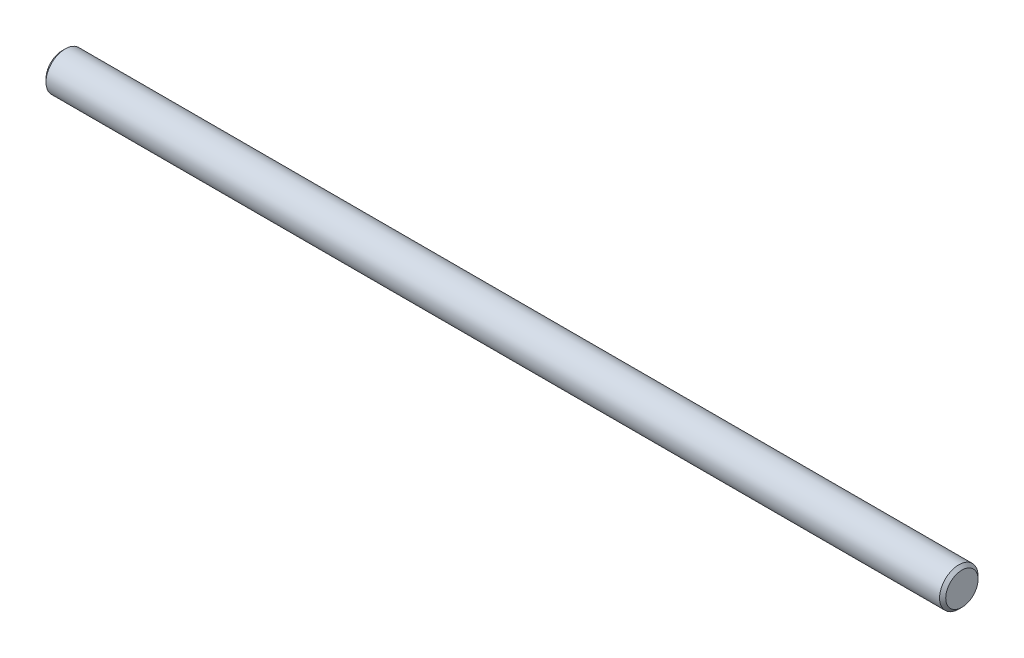
SolidWorks part; units mm, degrees
material "EN 1.3505 Equiv."
ref_plane "Front Plane" through (0, 0, 0) normal (0, 0, 1) x (1, 0, 0)
ref_plane "Top Plane" through (0, 0, 0) normal (0, 1, 0) x (1, 0, 0)
ref_plane "Right Plane" through (0, 0, 0) normal (1, 0, 0) x (0, 0, -1)
sketch "Sketch1" plane through (0, 0, 0) normal (0, 0, 1) x (1, 0, 0)
  line L0 (0, 0) -> (117, 0) construction
  line L3 (0, 0) -> (117, 0)
  line L4 (0, 0) -> (0, 2.5)
  line L5 (0, 2.5) -> (117, 2.5)
  line L6 (117, 0) -> (117, 2.5)
  dimension "D" = 5
  dimension "L" = 117
revolve "Revolve1" add sketch "Sketch1" angle 360 about L0
chamfer "Chamfer1" distance 0.4 angle 45 2 edges at (117, 0, 2.5) (0, 0, 2.5)
ref_plane "Plane1" through (0, 0, 2.5) normal (0, 0, 1) x (1, 0, 0)
ref_plane "Plane2" through (117, 0, 0) normal (1, 0, 0) x (0, 0, -1)
ref_plane "Dim. A" through (2, 0, 0) normal (-1, 0, 0) x (0, 0, 1)
ref_plane "Dim. SC" [suppressed] through (2, 0, 0) normal (-1, 0, 0) x (0, 0, 1)
sketch "Sketch2" [suppressed] plane through (0, 0, 0) normal (0, 1, 0) x (1, 0, 0)
  line L0 (0, 0) -> (76, 0) construction
  line L1 (2, -6) -> (12, -6)
  line L2 (2, -6) -> (2, -5)
  line L3 (2, -5) -> (12, -5)
  line L4 (12, -6) -> (12, -5)
  line L5 (7, -5) -> (7, -6) construction
  line L6 (2, 6) -> (12, 6)
  line L7 (2, 6) -> (2, 5)
  line L8 (2, 5) -> (12, 5)
  line L9 (12, 6) -> (12, 5)
  line L11 (2, 5.5) -> (2, -5.5) construction
  dimension "L1_s" = 10
  dimension "W_1" = 10
  dimension "D" = 5
  dimension "L1_s_L" = 10
extrude "Cut-Extrude1" [suppressed] cut sketch "Sketch2" against normal through all and the other way through all
ref_plane "SC_SEC" [suppressed] through (7, 0, 0) normal (1, 0, 0) x (0, 0, -1)
ref_plane "Dim. WSC" [suppressed] through (2, 0, 0) normal (-1, 0, 0) x (0, 0, 1)
ref_plane "Dim. X" [suppressed] through (74, 0, 0) normal (1, 0, 0) x (0, 0, -1)
sketch "Sketch3" [suppressed] plane through (0, 0, 0) normal (0, 1, 0) x (1, 0, 0)
  line L0 (0, 0) -> (76, 0) construction
  line L1 (2, -6) -> (12, -6)
  line L2 (2, -6) -> (2, -5)
  line L3 (2, -5) -> (12, -5)
  line L4 (12, -6) -> (12, -5)
  line L5 (2, 5.5) -> (2, -5.5) construction
  line L6 (2, 6) -> (12, 6)
  line L7 (2, 6) -> (2, 5)
  line L8 (2, 5) -> (12, 5)
  line L9 (12, 6) -> (12, 5)
  line L10 (7, -5) -> (7, -6) construction
  line L11 (64, 6) -> (74, 6)
  line L12 (64, 6) -> (64, 5)
  line L13 (64, 5) -> (74, 5)
  line L14 (74, 6) -> (74, 5)
  line L15 (64, -6) -> (74, -6)
  line L16 (64, -6) -> (64, -5)
  line L17 (64, -5) -> (74, -5)
  line L18 (74, -6) -> (74, -5)
  line L19 (74, -2.6075) -> (74, 2.6075) construction
  line L20 (69, -5) -> (69, -6) construction
  dimension "L1_s" = 10
  dimension "W_1" = 10
  dimension "D" = 5
  dimension "L1_s_L1" = 10
  dimension "L1_s_R2" = 10
  dimension "L1_s_R1" = 10
  dimension "W_1_R" = 10
extrude "Cut-Extrude2" [suppressed] cut sketch "Sketch3" against normal through all and the other way through all
ref_plane "WSC_SEC1" [suppressed] through (7, 0, 0) normal (1, 0, 0) x (0, 0, -1)
ref_plane "WSC_SEC2" [suppressed] through (69, 0, 0) normal (1, 0, 0) x (0, 0, -1)
sketch "Sketch4" [suppressed] plane through (0, 0, 0) normal (0, 0, 1) x (1, 0, 0)
  line L0 (2, 5.5) -> (2, -5.5) construction
  line L1 (2, 6) -> (7, 6)
  line L2 (2, 6) -> (2, 5)
  line L3 (2, 5) -> (7, 5)
  line L4 (7, 6) -> (7, 5)
  line L5 (0, 0) -> (76, 0) construction
  line L6 (4.5, 6) -> (4.5, 5) construction
  line L7 (0, 6) -> (76, 6) construction
  dimension "FC" = 5
  dimension "H_s_1" = 1
extrude "Cut-Extrude3" [suppressed] cut sketch "Sketch4" against normal through all and the other way through all
ref_plane "FC_SEC" [suppressed] through (4.5, 0, 0) normal (1, 0, 0) x (0, 0, -1)
ref_plane "Dim. E" [suppressed] through (74, 0, 0) normal (1, 0, 0) x (0, 0, -1)
sketch "Sketch5" [suppressed] plane through (0, 0, 0) normal (0, 0, 1) x (1, 0, 0)
  line L0 (4.5, 6) -> (4.5, 5) construction
  line L1 (2, 6) -> (7, 6)
  line L2 (2, 6) -> (2, 5)
  line L3 (2, 5) -> (7, 5)
  line L4 (7, 6) -> (7, 5)
  line L5 (2, 5.5) -> (2, -5.5) construction
  line L6 (74, 6) -> (69, 6)
  line L7 (74, 6) -> (74, 5)
  line L8 (74, 5) -> (69, 5)
  line L9 (69, 6) -> (69, 5)
  line L10 (0, 0) -> (76, 0) construction
  line L11 (71.5, 6) -> (71.5, 5) construction
  line L12 (74, -5.775) -> (74, 5.775) construction
  line L13 (0, 6) -> (76, 6) construction
  dimension "WFC" = 5
  dimension "H_s_1" = 1
  dimension "WFC_R" = 5
  dimension "H_s_1_R" = 1
extrude "Cut-Extrude4" [suppressed] cut sketch "Sketch5" against normal through all and the other way through all
ref_plane "WFC_SEC1" [suppressed] through (4.5, 0, 0) normal (1, 0, 0) x (0, 0, -1)
ref_plane "WFC_SEC2" [suppressed] through (71.5, 0, 0) normal (1, 0, 0) x (0, 0, -1)
sketch "Sketch6" [suppressed] plane through (0, 0, 0) normal (0, 0, 1) x (1, 0, 0)
  line L0 (0, 0) -> (76, 0) construction
  line L1 (2, 6) -> (8, 6)
  line L2 (2, 6) -> (2, 5)
  line L3 (2, 5) -> (8, 5)
  line L4 (8, 6) -> (8, 5)
  line L5 (0, 5.6) -> (0, -5.6) construction
  line L6 (5, 6) -> (5, 5) construction
  dimension "D" = 5
  dimension "H_s_2" = 1
  dimension "B1_s" = 6
  dimension "RC" = 2
extrude "Cut-Extrude5" [suppressed] cut sketch "Sketch6" against normal through all and the other way through all
pattern_circular "CirPattern1" [suppressed] count 2 every 90 reverse direction yes of bodies 106
ref_plane "Plane3" [suppressed] through (0, 0, 0) normal (0, 1, 0) x (1, 0, 0)
sketch "Sketch12" [suppressed] plane through (0, 0, 0) normal (0, 1, 0) x (1, 0, 0)
  line L0 (0, 0) -> (76, 0) construction
  line L1 (2, -6) -> (8, -6)
  line L2 (2, -6) -> (2, -5)
  line L3 (2, -5) -> (8, -5)
  line L4 (8, -6) -> (8, -5)
  dimension "D" = 5
  dimension "H_s_2" = 1
  dimension "B1_s" = 6
  dimension "RC" = 2
ref_plane "RC_SEC" [suppressed] through (5, 0, 0) normal (1, 0, 0) x (0, 0, -1)
sketch "Sketch13" [suppressed] plane through (5, 0, 0) normal (1, 0, 0) x (0, 0, -1)
  line L0 (-6, 0) -> (-5, 0) construction
  line L1 (-6, 0) -> (-5, 0) construction
  line L2 (0, 6) -> (0, 5) construction
  line L3 (0, 6) -> (0, 5) construction
  line L4 (-3.3166, 5) -> (3.3166, 5) construction
  line L5 (-5, 3.3166) -> (-5, -3.3166) construction
  circle A0 centre (0, 0) radius 6 construction
  dimension "ANG" = 90
sketch "Sketch7" [suppressed] plane through (0, 0, 0) normal (0, 0, 1) x (1, 0, 0)
  line L0 (5, 6) -> (5, 5) construction
  line L1 (2, 6) -> (8, 6)
  line L2 (2, 6) -> (2, 5)
  line L3 (2, 5) -> (8, 5)
  line L4 (8, 6) -> (8, 5)
  line L6 (68, 6) -> (74, 6)
  line L7 (68, 6) -> (68, 5)
  line L8 (68, 5) -> (74, 5)
  line L9 (74, 6) -> (74, 5)
  line L11 (0, 0) -> (76, 0) construction
  line L12 (71, 6) -> (71, 5) construction
  dimension "D" = 5
  dimension "H_s_2" = 1
  dimension "B1_s" = 6
  dimension "H_s_2_R" = 1
  dimension "B1_s_R" = 6
  dimension "WRC" = 2
  dimension "Y" = 2
extrude "Cut-Extrude6" [suppressed] cut sketch "Sketch7" against normal through all and the other way through all
pattern_circular "CirPattern2" [suppressed] count 2 every 90 reverse direction yes of bodies 108
ref_plane "Plane4" [suppressed] through (0, 0, 0) normal (0, 1, 0) x (1, 0, 0)
sketch "Sketch14" [suppressed] plane through (0, 0, 0) normal (0, 1, 0) x (1, 0, 0)
  line L0 (0, 0) -> (76, 0) construction
  line L1 (2, -6) -> (8, -6)
  line L2 (2, -6) -> (2, -5)
  line L3 (2, -5) -> (8, -5)
  line L4 (8, -6) -> (8, -5)
  line L5 (68, -6) -> (74, -6)
  line L6 (68, -6) -> (68, -5)
  line L7 (68, -5) -> (74, -5)
  line L8 (74, -6) -> (74, -5)
  dimension "D" = 5
  dimension "H_s_2" = 1
  dimension "B1_s" = 6
  dimension "H_s_2_R" = 1
  dimension "B1_s_R" = 6
  dimension "WRC" = 2
  dimension "Y" = 2
ref_plane "WRC_SEC1" [suppressed] through (5, 0, 0) normal (1, 0, 0) x (0, 0, -1)
sketch "Sketch15" [suppressed] plane through (5, 0, 0) normal (1, 0, 0) x (0, 0, -1)
  line L0 (0, 6) -> (0, 5) construction
  line L1 (-6, 0) -> (-5, 0) construction
  line L2 (0, 6) -> (0, 5) construction
  line L3 (-6, 0) -> (-5, 0) construction
  line L4 (-3.3166, 5) -> (3.3166, 5) construction
  line L5 (-5, 3.3166) -> (-5, -3.3166) construction
  circle A0 centre (0, 0) radius 6 construction
  dimension "ANG_L" = 90
ref_plane "WRC_SEC2" [suppressed] through (71, 0, 0) normal (1, 0, 0) x (0, 0, -1)
sketch "Sketch16" [suppressed] plane through (71, 0, 0) normal (1, 0, 0) x (0, 0, -1)
  line L0 (0, 6) -> (0, 5) construction
  line L1 (-6, 0) -> (-5, 0) construction
  line L2 (0, 6) -> (0, 5) construction
  line L3 (-6, 0) -> (-5, 0) construction
  line L4 (-3.3166, 5) -> (3.3166, 5) construction
  line L5 (-5, 3.3166) -> (-5, -3.3166) construction
  circle A0 centre (0, 0) radius 6 construction
  dimension "ANG_R" = 90
sketch "Sketch8" [suppressed] plane through (0, 0, 0) normal (0, 0, 1) x (1, 0, 0)
  line L0 (5, 6) -> (5, 4) construction
  line L3 (0, 5.6) -> (0, -5.6) construction
  line L4 (3, 6) -> (5, 4)
  line L5 (5, 4) -> (7, 6)
  line L6 (7, 6) -> (3, 6)
  line L7 (0, 0) -> (76, 0) construction
  dimension "D1" = 90
  dimension "VC" = 5
  dimension "W_2" = 4
  dimension "D" = 5
revolve "Cut-Revolve1" [suppressed] cut sketch "Sketch8" angle 360 about L7
sketch "Sketch9" [suppressed] plane through (0, 0, 0) normal (0, 0, 1) x (1, 0, 0)
  line L0 (5, 6) -> (5, 4) construction
  line L2 (71, 4) -> (71, 6) construction
  line L4 (0, 0) -> (76, 0) construction
  line L6 (0, 5.6) -> (0, -5.6) construction
  line L7 (3, 6) -> (5, 4)
  line L8 (5, 4) -> (7, 6)
  line L9 (7, 6) -> (3, 6)
  line L10 (69, 6) -> (71, 4)
  line L11 (71, 4) -> (73, 6)
  line L12 (73, 6) -> (69, 6)
  dimension "D1" = 90
  dimension "F" = 5
  dimension "WVC" = 66
  dimension "W_2" = 4
  dimension "D2" = 90
  dimension "D" = 5
  dimension "W_2_R" = 4
revolve "Cut-Revolve2" [suppressed] cut sketch "Sketch9" angle 360 about L4
ref_plane "Dim. KC_1" [suppressed] through (2, 0, 0) normal (1, 0, 0) x (0, 0, -1)
sketch "Sketch10" [suppressed] plane through (0, 0, 6) normal (0, 0, 1) x (1, 0, 0)
  line L0 (0, 0) -> (7, 0) construction
  line L1 (7, -2) -> (7, 2)
  line L2 (7, 2) -> (2, 2)
  line L3 (2, 2) -> (2, -2)
  line L4 (2, -2) -> (7, -2)
  line L5 (2, -6.6) -> (2, 6.6) construction
  line L6 (4.5, 2) -> (4.5, -2) construction
  point P9 (2, 0)
  dimension "G" = 5
  dimension "B_s" = 4
extrude "Boss-Extrude1" [suppressed] add sketch "Sketch10" against normal blind 2.5 separate body
fillet "Fillet1" [suppressed] type full round
fillet "Fillet2" [suppressed] type full round
fillet "Fillet3" [suppressed] radius 0.1
fillet "Fillet4" [suppressed] radius 0.1
combine bodies "Combine1" [suppressed] operation type subtract main body 101 bodies to subtract 118
ref_plane "KC_SEC" [suppressed] through (4.5, 0, 0) normal (1, 0, 0) x (0, 0, -1)
ref_plane "Dim. KC_2" [suppressed] through (2, 0, 0) normal (1, 0, 0) x (0, 0, -1)
ref_plane "Dim. WKC" [suppressed] through (74, 0, 0) normal (1, 0, 0) x (0, 0, -1)
sketch "Sketch11" [suppressed] plane through (0, 0, 6) normal (0, 0, 1) x (1, 0, 0)
  line L0 (0, 0) -> (76, 0) construction
  line L1 (4.5, 2) -> (4.5, -2) construction
  line L2 (71.5, 2) -> (71.5, -2) construction
  line L3 (2, -6.6) -> (2, 6.6) construction
  line L4 (74, 2) -> (69, 2)
  line L5 (74, 2) -> (74, -2)
  line L6 (74, -2) -> (69, -2)
  line L7 (69, 2) -> (69, -2)
  line L8 (7, 2) -> (2, 2)
  line L9 (7, 2) -> (7, -2)
  line L10 (7, -2) -> (2, -2)
  line L11 (2, 2) -> (2, -2)
  line L12 (74, -6.6) -> (74, 6.6) construction
  dimension "B_s" = 4
  dimension "G" = 5
  dimension "C" = 5
  dimension "B_s_R" = 4
extrude "Boss-Extrude2" [suppressed] add sketch "Sketch11" against normal blind 2.5 separate body
fillet "Fillet5" [suppressed] type full round
fillet "Fillet6" [suppressed] type full round
fillet "Fillet7" [suppressed] radius 0.1
fillet "Fillet8" [suppressed] type full round
fillet "Fillet9" [suppressed] type full round
fillet "Fillet10" [suppressed] radius 0.1
combine bodies "Combine2" [suppressed] operation type subtract main body 101 bodies to subtract 116 115
ref_plane "WKC_SEC1" [suppressed] through (4.5, 0, 0) normal (1, 0, 0) x (0, 0, -1)
ref_plane "WKC_SEC2" [suppressed] through (71.5, 0, 0) normal (1, 0, 0) x (0, 0, -1)
equation "\"Plane dim\"= \"D@Sketch1\" * 0.5"
equation "\"D@Sketch12\"=\"D@Sketch6\""
equation "\"H_s_2@Sketch12\"=\"H_s_2@Sketch6\""
equation "\"RC@Sketch12\"=\"RC@Sketch6\""
equation "\"B1_s@Sketch12\"=\"B1_s@Sketch6\""
equation "\"D@Sketch14\"=\"D@Sketch7\""
equation "\"H_s_2@Sketch14\"=\"H_s_2@Sketch7\""
equation "\"WRC@Sketch14\"=\"WRC@Sketch7\""
equation "\"B1_s@Sketch14\"=\"B1_s@Sketch7\""
equation "\"Y@Sketch14\"=\"Y@Sketch7\""
